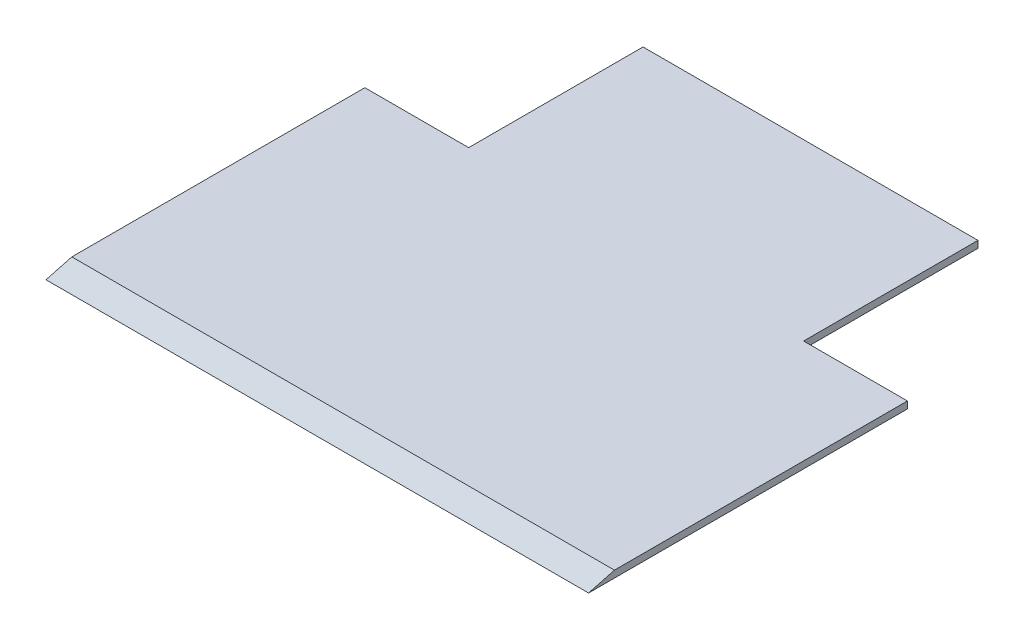
SolidWorks part; units mm, degrees
ref_plane "Alzado" through (0, 0, 0) normal (0, 0, 1) x (1, 0, 0)
ref_plane "Planta" through (0, 0, 0) normal (0, 1, 0) x (1, 0, 0)
ref_plane "Vista lateral" through (0, 0, 0) normal (1, 0, 0) x (0, 0, -1)
sketch "Croquis1" plane through (0, 0, 0) normal (1, 0, 0) x (0, 0, -1)
  line L0 (0, 0) -> (178.17, 0)
  line L1 (178.17, 0) -> (178.17, 2.5)
  line L2 (178.17, 2.5) -> (9.3301, 2.5)
  line L3 (0, 0) -> (9.3301, 2.5)
  dimension "D1" = 178.17
  dimension "D2" = 2.5
  dimension "D3" = 165
extrude "Saliente-Extruir1" add sketch "Croquis1" along normal blind 196
sketch "Croquis2" plane through (0, 0, 0) normal (0, -1, 0) x (-1, 0, 0)
  line L1 (-37.5, 115.1801) -> (0, 115.1801)
  line L2 (-37.5, 115.1801) -> (-37.5, 178.17)
  line L3 (-37.5, 178.17) -> (0, 178.17)
  line L4 (0, 115.1801) -> (0, 178.17)
  line L5 (-37.5, 115.1801) -> (0, 178.17) construction
  line L6 (-37.5, 178.17) -> (0, 115.1801) construction
  line L7 (-158.5, 115.1801) -> (-196, 115.1801)
  line L8 (-158.5, 115.1801) -> (-158.5, 178.17)
  line L9 (-158.5, 178.17) -> (-196, 178.17)
  line L10 (-196, 115.1801) -> (-196, 178.17)
  line L11 (-158.5, 115.1801) -> (-196, 178.17) construction
  line L12 (-158.5, 178.17) -> (-196, 115.1801) construction
  point P4 (-18.75, 146.6751)
  point P11 (-177.25, 146.6751)
extrude "Cortar-Extruir1" cut sketch "Croquis2" against normal up to next
